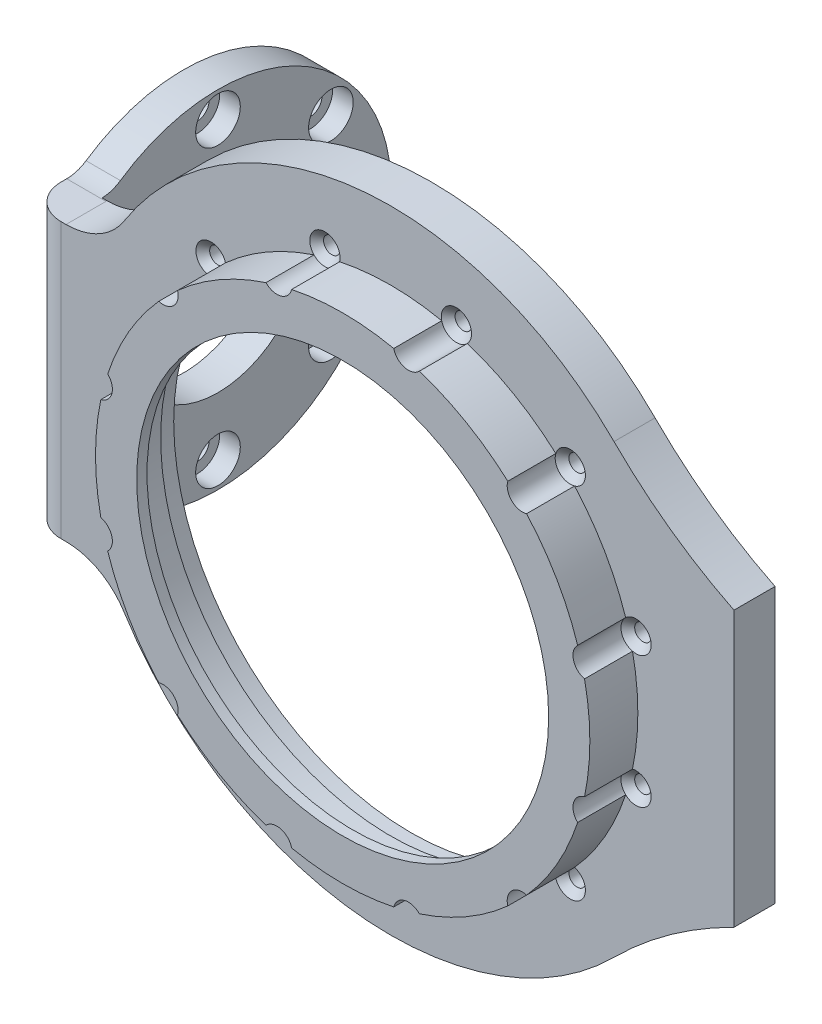
SolidWorks part; units mm, degrees
ref_plane "前视基准面" through (0, 0, 0) normal (0, 0, 1) x (1, 0, 0)
ref_plane "上视基准面" through (0, 0, 0) normal (0, 1, 0) x (1, 0, 0)
ref_plane "右视基准面" through (0, 0, 0) normal (1, 0, 0) x (0, 0, -1)
sketch "草图3" plane through (0, 0, 0) normal (0, 0, 1) x (1, 0, 0)
  circle A0 centre (0, 0) radius 34.6
  circle A1 centre (0, 0) radius 46
extrude "凸台-拉伸2" add sketch "草图3" along normal blind 3
ref_plane "基准面5" through (0, 0, 3) normal (0, 0, 1) x (1, 0, 0)
sketch "草图5" plane through (0, 0, 3) normal (0, 0, 1) x (1, 0, 0)
  circle A0 centre (0, 0) radius 33.5
  circle A1 centre (0, 0) radius 36
extrude "凸台-拉伸3" add sketch "草图5" along normal blind 5.49
sketch "草图2" plane through (0, 0, 0) normal (0, 0, 1) x (1, 0, 0)
  circle A0 centre (0, 0) radius 41.6
  circle A1 centre (0, 0) radius 46
extrude "凸台-拉伸1" add sketch "草图2" against normal blind 2.98
sketch "草图6" plane through (0, 0, 8.49) normal (0, 0, 1) x (1, 0, 0)
  circle A0 centre (0, 0) radius 30
  circle A1 centre (0, 0) radius 36
extrude "凸台-拉伸4" add sketch "草图6" along normal blind 1.5
sketch "草图8" plane through (0, 0, 0) normal (0, 0, 1) x (1, 0, 0)
  line L1 (-50, -20) -> (-50, 20)
  line L3 (50, -20) -> (50, 20)
  line L4 (-50, 20) -> (-41.4246, 20)
  line L5 (-50, -20) -> (-41.4246, -20)
  arc A5 (32.5269, 32.5269) -> (32.5269, -32.5269) centre (0, 0) cw
  arc A6 (50, -20) -> (32.5269, -32.5269) centre (79.2531, -79.2531) ccw
  arc A7 (50, 20) -> (32.5269, 32.5269) centre (79.2531, 79.2531) cw
  circle A8 centre (0, 0) radius 46 construction
  arc A9 (-41.4246, -20) -> (-41.4246, 20) centre (0, 0) cw
extrude "凸台-拉伸5" add sketch "草图8" along normal blind 3 and the other way blind 2.98
hole_wizard "M2 锥坑平头的锥孔1" positions "3D草图3" profile "草图12" countersink size "M2" standard "BSI" end condition through all
sketch3d "3D草图3"
  line L2 (0, 0, 0) -> (0, 37, 0)
  line L3 (0, 0, 0) -> (11.5811, 0, 0)
  point P55 (9.5763, 35.7393, 3)
  point P76 (26.163, 26.163, 3)
  point P83 (35.7393, 9.5763, 3)
  point P96 (-35.7393, 9.5763, 3)
  point P97 (-26.163, 26.163, 3)
  point P98 (-9.5763, 35.7393, 3)
  point P99 (35.7393, -9.5763, 3)
  point P100 (26.163, -26.163, 3)
  point P101 (9.5763, -35.7393, 3)
  point P102 (-9.5763, -35.7393, 3)
  point P103 (-26.163, -26.163, 3)
  point P104 (-35.7393, -9.5763, 3)
sketch "草图12" plane through (-35.7393, -9.5763, 3) normal (1, 0, 0) x (0, -1, 0)
  line L0 (0, 0) -> (0, 5.98)
  line L1 (0, 5.98) -> (1.2, 5.98)
  line L2 (1.2, 5.98) -> (1.2, 1)
  line L3 (1.2, 1) -> (2.2, 0)
  line L5 (2.2, 0) -> (0, 0)
  line L6 (-1.2, 1) -> (-2.2, 0) construction
  line L11 (0, -6.35) -> (0, 107.95) construction
  dimension "通孔孔直径" = 2.4
  dimension "通孔孔深度" = 5.98
  dimension "近端锥形沉头孔直径" = 4.4
  dimension "近端锥形沉头孔角度" = 90
sketch "草图13" plane through (0, 0, 3) normal (0, 0, 1) x (1, 0, 0)
  line L0 (0, 0) -> (0, 10.9464)
  line L1 (0, 0) -> (8.3109, 0)
  circle A0 centre (-35.7393, 9.5763) radius 2.2
  circle A1 centre (-26.163, 26.163) radius 2.2
  circle A2 centre (-9.5763, 35.7393) radius 2.2
  circle A3 centre (-9.5763, -35.7393) radius 2.2
  circle A4 centre (-26.163, -26.163) radius 2.2
  circle A5 centre (-35.7393, -9.5763) radius 2.2
  circle A6 centre (9.5763, -35.7393) radius 2.2
  circle A7 centre (26.163, -26.163) radius 2.2
  circle A8 centre (9.5763, 35.7393) radius 2.2
  circle A9 centre (26.163, 26.163) radius 2.2
  circle A10 centre (35.7393, -9.5763) radius 2.2
  circle A11 centre (35.7393, 9.5763) radius 2.2
extrude "切除-拉伸1" cut sketch "草图13" along normal up to next contours A5 | A4 | A0 | A1 | A2 | A9 | A11 | A10 | A6 | A3 | A8 | A7 region at (-35.7393, 9.5763, 3) region at (-26.163, 26.163, 3) region at (-9.5763, 35.7393, 3) region at (-9.5763, -35.7393, 3) region at (-26.163, -26.163, 3) region at (-35.7393, -9.5763, 3) region at (9.5763, -35.7393, 3) region at (26.163, 26.163, 3) region at (35.7393, -9.5763, 3) region at (35.7393, 9.5763, 3)
ref_plane "基准面6" through (-50, 0, 0) normal (-1, 0, 0) x (0, 0, 1)
sketch "草图14" plane through (-50, 0, 0) normal (-1, 0, 0) x (0, 0, 1)
  line L0 (-4.4369, 20) -> (3, 20)
  line L3 (3, 20) -> (3, -20)
  line L5 (-4.4369, -20) -> (3, -20)
  arc A1 (-4.4369, -20) -> (-4.4369, 20) centre (-19.85, 0) cw
extrude "凸台-拉伸6" add sketch "草图14" along normal blind 3 and the other way blind 2
fillet "圆角1" radius 10 1 edges at (-41.4246, 20, 0.01)
fillet "圆角2" radius 10 1 edges at (-41.4246, -20, 0.01)
fillet "圆角3" radius 5 1 edges at (-50.5, 20, -4.4369)
fillet "圆角4" radius 5 1 edges at (-53, 0, 3)
fillet "圆角5" radius 5 1 edges at (-50.5, -20, -4.4369)
ref_plane "基准面7" through (-48, -20.0026, -2.98) normal (0, 1, 0) x (1, 0, 0)
sketch "草图17" plane through (-48, -20.0026, -2.98) normal (0, 1, 0) x (1, 0, 0)
  line L0 (0, 0) -> (0, 5)
  line L1 (0, 2.6539) -> (0, 42.12) construction
  line L2 (0, 0) -> (5, 0)
  line L3 (9.1576, 0) -> (0.4856, 0) construction
  arc A1 (0, 5) -> (5, 0) centre (5, 5) ccw
sketch "草图19" plane through (-50, 0, 0) normal (-1, 0, 0) x (0, 0, 1)
  circle A1 centre (-19.85, 0) radius 13
extrude "切除-拉伸3" cut sketch "草图19" against normal through all and the other way through all contours A1
hole_wizard "M3 六角凹头盖的柱孔1" positions "3D草图4" profile "草图20" counterbore size "M3" standard "BSI" end condition up to next
sketch3d "3D草图4"
  point P0 (-48, 21.4664, -19.85)
  point P42 (-48, 13.7984, -36.2942)
  point P61 (-48, 13.7984, -3.4058)
  point P72 (-48, -13.7984, -36.2942)
  point P74 (-48, -21.4664, -19.85)
  point P76 (-48, -13.7984, -3.4058)
sketch "草图20" plane through (-48, 21.4664, -19.85) normal (0, 1, 0) x (0, 0, -1)
  line L0 (0, 0) -> (0, 5)
  line L1 (0, 5) -> (1.7, 5)
  line L3 (1.7, 5) -> (1.7, 3)
  line L4 (1.7, 3) -> (3.25, 3)
  line L5 (3.25, 3) -> (3.25, 0)
  line L7 (3.25, 0) -> (0, 0)
  line L11 (0, -6.35) -> (0, 107.95) construction
  dimension "通孔孔直径" = 3.4
  dimension "通孔孔深度" = 5
  dimension "柱形沉头孔直径" = 6.5
  dimension "柱形沉头孔深度" = 3
sketch "草图21" plane through (-50, 0, 0) normal (-1, 0, 0) x (0, 0, 1)
  circle A0 centre (-3.4058, 13.7984) radius 3.25
  circle A1 centre (-3.4058, -13.7984) radius 3.25
extrude "切除-拉伸4" cut sketch "草图21" against normal blind 15
